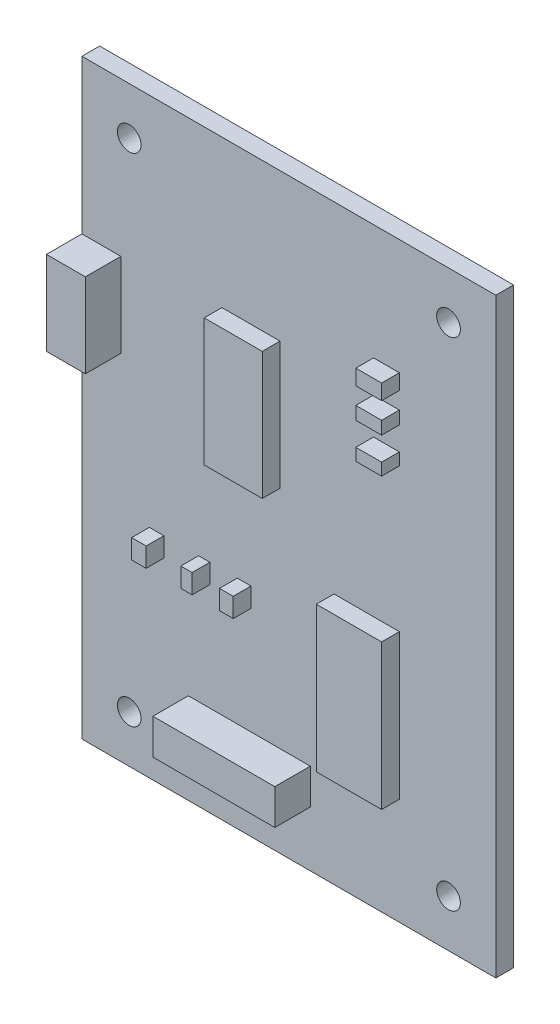
SolidWorks part; units mm, degrees
ref_plane "Спереди" through (0, 0, 0) normal (0, 0, 1) x (1, 0, 0)
ref_plane "Сверху" through (0, 0, 0) normal (0, 1, 0) x (1, 0, 0)
ref_plane "Справа" through (0, 0, 0) normal (1, 0, 0) x (0, 0, -1)
sketch "Эскиз1" plane through (0, 0, 0) normal (0, 0, 1) x (1, 0, 0)
  line L1 (0, 0) -> (70, 0)
  line L2 (0, 0) -> (0, 100)
  line L3 (0, 100) -> (70, 100)
  line L4 (70, 0) -> (70, 100)
  dimension "D1" = 70
  dimension "D2" = 100
extrude "Бобышка-Вытянуть1" add sketch "Эскиз1" along normal blind 3
sketch "Эскиз2" plane through (0, 0, 3) normal (0, 0, 1) x (1, 0, 0)
  line L0 (70, 100) -> (0, 100) construction
  line L1 (0, 100) -> (0, 0) construction
  line L2 (70, 50) -> (0, 50) construction
  line L3 (70, 0) -> (70, 100) construction
  circle A0 centre (8, 92) radius 2
  circle A1 centre (62, 92) radius 2
  circle A2 centre (62, 8) radius 2
  circle A3 centre (8, 8) radius 2
  point P12 (0, 0)
  dimension "D1" = 4
  dimension "D2" = 8
  dimension "D3" = 8
  dimension "D4" = 8
extrude "Вырез-Вытянуть1" cut sketch "Эскиз2" against normal through all
sketch "Эскиз3" plane through (0, 0, 3) normal (0, 0, 1) x (1, 0, 0)
  line L1 (23.68, 75.0266) -> (33.4998, 75.0266)
  line L2 (23.68, 75.0266) -> (23.68, 53.4778)
  line L3 (23.68, 53.4778) -> (33.4998, 53.4778)
  line L4 (33.4998, 75.0266) -> (33.4998, 53.4778)
  line L5 (42.6376, 42.567) -> (53.6847, 42.567)
  line L6 (42.6376, 42.567) -> (42.6376, 18.0177)
  line L7 (42.6376, 18.0177) -> (53.6847, 18.0177)
  line L8 (53.6847, 42.567) -> (53.6847, 18.0177)
  line L9 (11.4054, 36.7025) -> (13.8603, 36.7025)
  line L10 (11.4054, 36.7025) -> (11.4054, 33.4292)
  line L11 (11.4054, 33.4292) -> (13.8603, 33.4292)
  line L12 (13.8603, 36.7025) -> (13.8603, 33.4292)
  line L13 (19.7249, 36.7025) -> (21.6343, 36.7025)
  line L14 (19.7249, 36.7025) -> (19.7249, 33.4292)
  line L15 (19.7249, 33.4292) -> (21.6343, 33.4292)
  line L16 (21.6343, 36.7025) -> (21.6343, 33.4292)
  line L17 (26.2714, 36.7025) -> (28.5899, 36.7025)
  line L18 (26.2714, 36.7025) -> (26.2714, 33.4292)
  line L19 (26.2714, 33.4292) -> (28.5899, 33.4292)
  line L20 (28.5899, 36.7025) -> (28.5899, 33.4292)
  line L21 (49.3204, 68.8893) -> (53.6847, 68.8893)
  line L22 (49.3204, 68.8893) -> (49.3204, 66.8435)
  line L23 (49.3204, 66.8435) -> (53.6847, 66.8435)
  line L24 (53.6847, 68.8893) -> (53.6847, 66.8435)
  line L25 (49.3204, 75.0266) -> (53.6847, 75.0266)
  line L26 (49.3204, 75.0266) -> (49.3204, 72.8445)
  line L27 (49.3204, 72.8445) -> (53.6847, 72.8445)
  line L28 (53.6847, 75.0266) -> (53.6847, 72.8445)
  line L29 (49.3204, 80.482) -> (53.6847, 80.482)
  line L30 (49.3204, 80.482) -> (49.3204, 77.8907)
  line L31 (49.3204, 77.8907) -> (53.6847, 77.8907)
  line L32 (53.6847, 80.482) -> (53.6847, 77.8907)
extrude "Бобышка-Вытянуть2" add sketch "Эскиз3" along normal blind 3
sketch "Эскиз4" plane through (0, 0, 3) normal (0, 0, 1) x (1, 0, 0)
  line L0 (0, 100) -> (0, 0) construction
  line L1 (0, 73.9849) -> (6.5823, 73.9849)
  line L2 (0, 73.9849) -> (0, 59.776)
  line L3 (0, 59.776) -> (6.5823, 59.776)
  line L4 (6.5823, 73.9849) -> (6.5823, 59.776)
  line L6 (18.0051, 15.3385) -> (38.6219, 15.3385)
  line L7 (18.0051, 15.3385) -> (18.0051, 9.3485)
  line L8 (18.0051, 9.3485) -> (38.6219, 9.3485)
  line L9 (38.6219, 15.3385) -> (38.6219, 9.3485)
extrude "Бобышка-Вытянуть3" add sketch "Эскиз4" along normal blind 6
